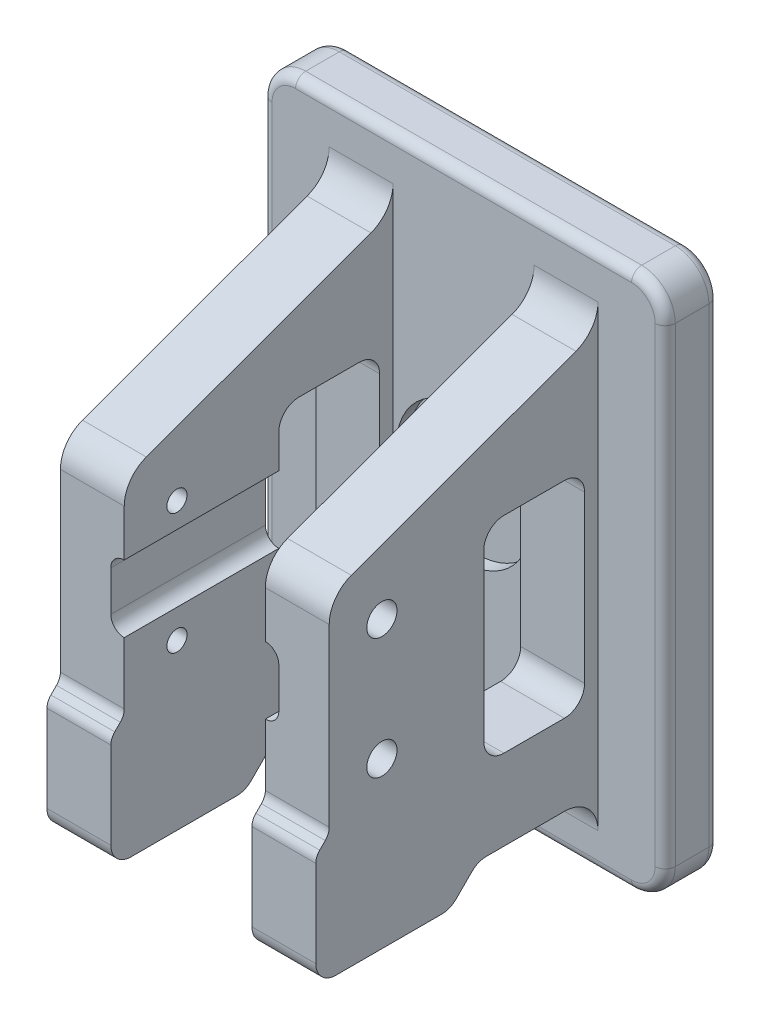
SolidWorks part; units mm, degrees
ref_plane "Front Plane" through (0, 0, 0) normal (0, 0, 1) x (1, 0, 0)
ref_plane "Top Plane" through (0, 0, 0) normal (0, 1, 0) x (1, 0, 0)
ref_plane "Right Plane" through (0, 0, 0) normal (1, 0, 0) x (0, 0, -1)
sketch "Sketch3" plane through (0, 0, 30) normal (0, 0, -1) x (-1, 0, 0)
  line L0 (95, 33.2573) -> (65, 33.2573) construction
  line L15 (80, 53.2573) -> (80, 33.2573) construction
  line L20 (55, 53.2573) -> (105, 53.2573)
  line L29 (55, -26.7427) -> (105, -26.7427)
  line L31 (110, -21.7427) -> (110, 48.2573)
  line L33 (50, -21.7427) -> (50, 48.2573)
  arc A17 (50, 48.2573) -> (55, 53.2573) centre (55, 48.2573) cw
  arc A18 (110, 48.2573) -> (105, 53.2573) centre (105, 48.2573) ccw
  arc A21 (50, -21.7427) -> (55, -26.7427) centre (55, -21.7427) ccw
  arc A22 (110, -21.7427) -> (105, -26.7427) centre (105, -21.7427) cw
  dimension "D1" = 5
extrude "Boss-Extrude1" add sketch "Sketch3" along normal blind 8
sketch "Sketch8" plane through (0, 0, 22) normal (0, 0, -1) x (-1, 0, 0)
  line L0 (50, 13.2573) -> (110, 13.2573) construction
  line L1 (50, 48.2573) -> (50, -21.7427) construction
  line L2 (110, -21.7427) -> (110, 48.2573) construction
  line L3 (80, 13.2573) -> (80, -26.7427) construction
  line L4 (55, -26.7427) -> (105, -26.7427) construction
  line L5 (78.25, 15.3786) -> (78.25, 11.136)
  line L6 (81.75, 15.3786) -> (81.75, 11.136)
  arc A0 (78.25, 11.136) -> (81.75, 11.136) centre (80, 13.2573) ccw
  arc A1 (81.75, 15.3786) -> (78.25, 15.3786) centre (80, 13.2573) ccw
extrude "Cut-Extrude3" cut sketch "Sketch8" against normal blind 3
sketch "Sketch10" plane through (0, 0, 22) normal (0, 0, -1) x (-1, 0, 0)
  line L0 (50, 13.2573) -> (110, 13.2573) construction
  line L1 (50, 48.2573) -> (50, -21.7427) construction
  line L2 (110, -21.7427) -> (110, 48.2573) construction
  line L3 (80, 13.2573) -> (80, -26.7427) construction
  line L4 (55, -26.7427) -> (105, -26.7427) construction
  line L7 (81.75, 11.136) -> (81.75, 15.3786)
  line L8 (78.25, 15.3786) -> (78.25, 11.136)
  line L9 (81.75, 11.136) -> (81.75, 15.3786)
  line L10 (78.25, 15.3786) -> (78.25, 11.136)
  circle A3 centre (80, 13.2573) radius 9.75
  arc A5 (78.25, 11.136) -> (81.75, 11.136) centre (80, 13.2573) ccw
  arc A6 (81.75, 15.3786) -> (78.25, 15.3786) centre (80, 13.2573) ccw
  arc A7 (78.25, 11.136) -> (81.75, 11.136) centre (80, 13.2573) ccw
  arc A8 (81.75, 15.3786) -> (78.25, 15.3786) centre (80, 13.2573) ccw
  dimension "D1" = 0
extrude "Boss-Extrude4" add sketch "Sketch10" along normal blind 9
fillet "Fillet2" radius 1.5 16 edges at (-80, -26.7427, 30) (-80, 53.2573, 30) (-50, 13.2573, 30) (-51.4645, 51.7928, 30) (-108.5355, 51.7928, 30) (-110, 13.2573, 30) (-80, -26.7427, 22) (-50, 13.2573, 22) (-51.4645, 51.7928, 22) (-80, 53.2573, 22) (-108.5355, 51.7928, 22) (-110, 13.2573, 22) (-108.5355, -25.2783, 22) (-51.4645, -25.2783, 22) (-108.5355, -25.2783, 30) (-51.4645, -25.2783, 30)
sketch "Sketch11" plane through (0, 0, 22) normal (0, 0, -1) x (-1, 0, 0)
  line L0 (50, 13.2573) -> (110, 13.2573) construction
  line L1 (50, -21.7427) -> (50, 48.2573) construction
  line L2 (110, 48.2573) -> (110, -21.7427) construction
  line L3 (80, 13.2573) -> (80, -26.7427) construction
  line L4 (105, -26.7427) -> (55, -26.7427) construction
  circle A0 centre (80, 13.2573) radius 11.75
extrude "Boss-Extrude5" add sketch "Sketch11" along normal blind 1
sketch "Sketch14" plane through (-70, 0, 0) normal (1, 0, 0) x (0, 0, -1)
  line L0 (-22, 1.5073) -> (-22, 25.0073) construction
  line L1 (-30, 48.2573) -> (-30, -21.7427) construction
  line L2 (-70, -1.7605) -> (-70, 28.6985)
  line L3 (-70, 28.6985) -> (-30, 43.2573)
  line L4 (-30, -16.3789) -> (-47.8764, -16.3789)
  line L6 (-30, -16.3789) -> (-30, 43.2573)
  line L7 (-47.8764, -16.3789) -> (-52, -20.5025)
  line L8 (-52, -20.5025) -> (-72, -20.5025)
  line L9 (-72, -20.5025) -> (-72, -3.7605)
  line L11 (-72, -3.7605) -> (-70, -1.7605)
  circle A6 centre (-62.1572, 3.9815) radius 1.5 construction
  circle A7 centre (-62.1572, 21.9815) radius 1.5 construction
  circle A8 centre (-62.1572, 3.9815) radius 1.5
  circle A9 centre (-62.1572, 21.9815) radius 1.5
extrude "Boss-Extrude7" add sketch "Sketch14" along normal blind 10
sketch "Sketch15" plane through (-90, 0, 0) normal (-1, 0, 0) x (0, 0, 1)
  line L4 (47.8764, -16.3789) -> (52, -20.5025)
  line L5 (70, -1.7605) -> (70, 28.6985)
  line L6 (70, 28.6985) -> (30, 43.2573)
  line L7 (30, 43.2573) -> (30, -16.3789)
  line L9 (70, -1.7605) -> (70, 28.6985)
  line L10 (70, 28.6985) -> (30, 43.2573)
  line L15 (30, 43.2573) -> (30, -16.3789)
  line L20 (47.8764, -16.3789) -> (52, -20.5025)
  line L21 (52, -20.5025) -> (72, -20.5025)
  line L22 (52, -20.5025) -> (72, -20.5025)
  line L23 (72, -20.5025) -> (72, -3.7605)
  line L24 (72, -20.5025) -> (72, -3.7605)
  line L25 (72, -3.7605) -> (70, -1.7605)
  line L26 (72, -3.7605) -> (70, -1.7605)
  line L27 (30, -16.3789) -> (47.8764, -16.3789)
  line L28 (30, -16.3789) -> (47.8764, -16.3789)
  circle A2 centre (62.1572, 3.9815) radius 1.5 construction
  circle A3 centre (62.1572, 21.9815) radius 1.5 construction
  circle A4 centre (62.1572, 3.9815) radius 1.5
  circle A5 centre (62.1572, 21.9815) radius 1.5
  dimension "D1" = 0
extrude "Boss-Extrude8" add sketch "Sketch15" along normal blind 10
fillet "Fillet3" radius 5 6 edges at (-65, 43.2573, 30) (-95, 43.2573, 30) (-95, 28.6985, 70) (-65, 28.6985, 70) (-95, -16.3789, 30) (-65, -16.3789, 30)
fillet "Fillet4" radius 3 6 edges at (-95, -20.5025, 72) (-65, -20.5025, 72) (-65, -20.5025, 52) (-95, -20.5025, 52) (-95, -16.3789, 47.8764) (-65, -16.3789, 47.8764)
sketch "Sketch16" plane through (-90, 0, 0) normal (1, 0, 0) x (0, 0, -1)
  line L8 (-72, -3.7605) -> (-72, -17.5025)
  line L9 (-69, -20.5025) -> (-53.2426, -20.5025)
  line L10 (-51.1213, -19.6238) -> (-48.7551, -17.2576)
  line L11 (-46.6337, -16.3789) -> (-35, -16.3789)
  line L12 (-30, -21.3789) -> (-30, 46.7583)
  line L13 (-33.2899, 42.0599) -> (-66.7101, 29.8959)
  line L14 (-70, 25.1974) -> (-70, -1.7605)
  line L15 (-70, -1.7605) -> (-72, -3.7605)
  line L16 (-72, -3.7605) -> (-72, -17.5025)
  line L17 (-69, -20.5025) -> (-53.2426, -20.5025)
  line L18 (-51.1213, -19.6238) -> (-48.7551, -17.2576)
  line L19 (-46.6337, -16.3789) -> (-35, -16.3789)
  line L20 (-30, -21.3789) -> (-30, 46.7583)
  line L21 (-33.2899, 42.0599) -> (-66.7101, 29.8959)
  line L22 (-70, 25.1974) -> (-70, -1.7605)
  line L23 (-70, -1.7605) -> (-72, -3.7605)
  arc A6 (-72, -17.5025) -> (-69, -20.5025) centre (-69, -17.5025) ccw
  arc A7 (-53.2426, -20.5025) -> (-51.1213, -19.6238) centre (-53.2426, -17.5025) ccw
  arc A8 (-46.6337, -16.3789) -> (-48.7551, -17.2576) centre (-46.6337, -19.3789) ccw
  arc A9 (-30, -21.3789) -> (-35, -16.3789) centre (-35, -21.3789) ccw
  arc A10 (-33.2899, 42.0599) -> (-30, 46.7583) centre (-35, 46.7583) ccw
  arc A11 (-66.7101, 29.8959) -> (-70, 25.1974) centre (-65, 25.1974) ccw
  arc A12 (-72, -17.5025) -> (-69, -20.5025) centre (-69, -17.5025) ccw
  arc A13 (-53.2426, -20.5025) -> (-51.1213, -19.6238) centre (-53.2426, -17.5025) ccw
  arc A14 (-46.6337, -16.3789) -> (-48.7551, -17.2576) centre (-46.6337, -19.3789) ccw
  arc A15 (-30, -21.3789) -> (-35, -16.3789) centre (-35, -21.3789) ccw
  arc A16 (-33.2899, 42.0599) -> (-30, 46.7583) centre (-35, 46.7583) ccw
  arc A17 (-66.7101, 29.8959) -> (-70, 25.1974) centre (-65, 25.1974) ccw
  dimension "D1" = 0
extrude "Cut-Extrude4" cut sketch "Sketch16" against normal blind 0.25
sketch "Sketch17" plane through (-70, 0, 0) normal (-1, 0, 0) x (0, 0, 1)
  line L8 (53.2426, -20.5025) -> (69, -20.5025)
  line L9 (72, -17.5025) -> (72, -3.7605)
  line L10 (72, -3.7605) -> (70, -1.7605)
  line L11 (70, -1.7605) -> (70, 25.1974)
  line L12 (66.7101, 29.8959) -> (33.2899, 42.0599)
  line L13 (30, 46.7583) -> (30, -21.3789)
  line L14 (35, -16.3789) -> (46.6337, -16.3789)
  line L15 (48.7551, -17.2576) -> (51.1213, -19.6238)
  line L16 (53.2426, -20.5025) -> (69, -20.5025)
  line L17 (72, -17.5025) -> (72, -3.7605)
  line L18 (72, -3.7605) -> (70, -1.7605)
  line L19 (70, -1.7605) -> (70, 25.1974)
  line L20 (66.7101, 29.8959) -> (33.2899, 42.0599)
  line L21 (30, 46.7583) -> (30, -21.3789)
  line L22 (35, -16.3789) -> (46.6337, -16.3789)
  line L23 (48.7551, -17.2576) -> (51.1213, -19.6238)
  arc A6 (69, -20.5025) -> (72, -17.5025) centre (69, -17.5025) ccw
  arc A7 (70, 25.1974) -> (66.7101, 29.8959) centre (65, 25.1974) ccw
  arc A8 (30, 46.7583) -> (33.2899, 42.0599) centre (35, 46.7583) ccw
  arc A9 (35, -16.3789) -> (30, -21.3789) centre (35, -21.3789) ccw
  arc A10 (48.7551, -17.2576) -> (46.6337, -16.3789) centre (46.6337, -19.3789) ccw
  arc A11 (51.1213, -19.6238) -> (53.2426, -20.5025) centre (53.2426, -17.5025) ccw
  arc A12 (69, -20.5025) -> (72, -17.5025) centre (69, -17.5025) ccw
  arc A13 (70, 25.1974) -> (66.7101, 29.8959) centre (65, 25.1974) ccw
  arc A14 (30, 46.7583) -> (33.2899, 42.0599) centre (35, 46.7583) ccw
  arc A15 (35, -16.3789) -> (30, -21.3789) centre (35, -21.3789) ccw
  arc A16 (48.7551, -17.2576) -> (46.6337, -16.3789) centre (46.6337, -19.3789) ccw
  arc A17 (51.1213, -19.6238) -> (53.2426, -20.5025) centre (53.2426, -17.5025) ccw
  dimension "D1" = 0
extrude "Cut-Extrude5" cut sketch "Sketch17" against normal blind 0.25
sketch "Sketch18" plane through (-100, 0, 0) normal (-1, 0, 0) x (0, 0, 1)
  line L1 (35, 26.2573) -> (44, 26.2573)
  line L2 (32, 23.2573) -> (32, -1.3789)
  line L3 (35, -4.3789) -> (44, -4.3789)
  line L4 (47, 23.2573) -> (47, -1.3789)
  arc A0 (44, -4.3789) -> (47, -1.3789) centre (44, -1.3789) ccw
  arc A1 (32, -1.3789) -> (35, -4.3789) centre (35, -1.3789) ccw
  arc A2 (35, 26.2573) -> (32, 23.2573) centre (35, 23.2573) ccw
  arc A3 (44, 26.2573) -> (47, 23.2573) centre (44, 23.2573) cw
  point P16 (32, 26.2573)
  point P19 (47, 26.2573)
extrude "Cut-Extrude6" cut sketch "Sketch18" against normal up to surface (40 mm away) up to face at (-60, -0.7658, 53.3813)
sketch "Sketch19" plane through (-60, 0, 0) normal (1, 0, 0) x (0, 0, -1)
  circle A0 centre (-62.1572, 21.9815) radius 2.25
  circle A1 centre (-62.1572, 3.9815) radius 2.25
extrude "Cut-Extrude7" cut sketch "Sketch19" against normal blind 4
chamfer "Chamfer1" distance 1.5 angle 45 2 edges at (-100, 2.4815, 62.1572) (-100, 20.4815, 62.1572)
sketch "Sketch20" plane through (0, 0, 72) normal (0, 0, 1) x (1, 0, 0)
  line L0 (-105, 53.2573) -> (-55, 53.2573) construction
  line L1 (-90.5, 53.2573) -> (-69.5, 53.2573)
  line L2 (-90.5, 53.2573) -> (-90.5, -26.7427)
  line L3 (-90.5, -26.7427) -> (-69.5, -26.7427)
  line L4 (-69.5, 53.2573) -> (-69.5, -26.7427)
  line L5 (-55, -26.7427) -> (-105, -26.7427) construction
  line L6 (-69.75, 46.7583) -> (-69.75, 42.0599) construction
  line L7 (-90.25, 42.0599) -> (-90.25, 29.8959) construction
  dimension "D1" = 0.25
  dimension "D2" = 0.25
extrude "Cut-Extrude8" cut sketch "Sketch20" against normal up to surface (42 mm away) up to face at (-95.125, 12.6897, 30)
fillet "Fillet5" radius 2 4 edges at (-95.25, -3.7605, 72) (-95.25, -1.7605, 70) (-64.75, -3.7605, 72) (-64.75, -1.7605, 70)
sketch "Sketch21" plane through (0, 0, 21) normal (0, 0, -1) x (-1, 0, 0)
  line L2 (81.75, 11.136) -> (81.75, 15.3786)
  line L3 (78.25, 15.3786) -> (78.25, 11.136)
  line L4 (81.75, 11.136) -> (81.75, 15.3786)
  line L5 (78.25, 15.3786) -> (78.25, 11.136)
  arc A2 (81.75, 15.3786) -> (78.25, 15.3786) centre (80, 13.2573) ccw
  arc A3 (78.25, 11.136) -> (81.75, 11.136) centre (80, 13.2573) ccw
  arc A4 (81.75, 15.3786) -> (78.25, 15.3786) centre (80, 13.2573) ccw
  arc A5 (78.25, 11.136) -> (81.75, 11.136) centre (80, 13.2573) ccw
  dimension "D1" = 0
extrude "Cut-Extrude9" cut sketch "Sketch21" against normal blind 5
sketch "Sketch22" plane through (0, 0, 30) normal (0, 0, 1) x (1, 0, 0)
  line L0 (-110, 13.2573) -> (-80, 13.2573) construction
  line L1 (-110, -21.7427) -> (-110, 48.2573) construction
  line L2 (-80, 13.2573) -> (-80, 53.2573) construction
  line L3 (-105, 53.2573) -> (-55, 53.2573) construction
  circle A0 centre (-80, 13.2573) radius 10
extrude "Cut-Extrude10" cut sketch "Sketch22" against normal blind 2
sketch "Sketch23" plane through (0, 0, 70) normal (0, 0, 1) x (1, 0, 0)
  line L0 (-90, 13.2573) -> (-70, 13.2573) construction
  line L1 (-90.5, -0.9321) -> (-90.5, 25.1974) construction
  line L2 (-90.5, 18.2573) -> (-92.5, 18.2573)
  line L3 (-90.5, 18.2573) -> (-90.5, 8.2573)
  line L4 (-90.5, 8.2573) -> (-92.5, 8.2573)
  line L5 (-92.5, 18.2573) -> (-92.5, 8.2573)
  line L6 (-69.5, 25.1974) -> (-69.5, -0.9321) construction
  line L7 (-69.5, 18.2573) -> (-67.5, 18.2573)
  line L8 (-69.5, 18.2573) -> (-69.5, 8.2573)
  line L9 (-69.5, 8.2573) -> (-67.5, 8.2573)
  line L10 (-67.5, 18.2573) -> (-67.5, 8.2573)
  circle A0 centre (-80, 13.2573) radius 10 construction
  dimension "D1" = 5
  dimension "D2" = 10
  dimension "D3" = 10
  dimension "D4" = 5
  dimension "D5" = 2
  dimension "D6" = 2
extrude "Cut-Extrude11" cut sketch "Sketch23" against normal up to surface (38 mm away) up to face at (-64.75, 10.9392, 32)
fillet "Fillet6" radius 2 4 edges at (-92.5, 8.2573, 58.5) (-92.5, 18.2573, 58.5) (-67.5, 8.2573, 58.5) (-67.5, 18.2573, 58.5)
